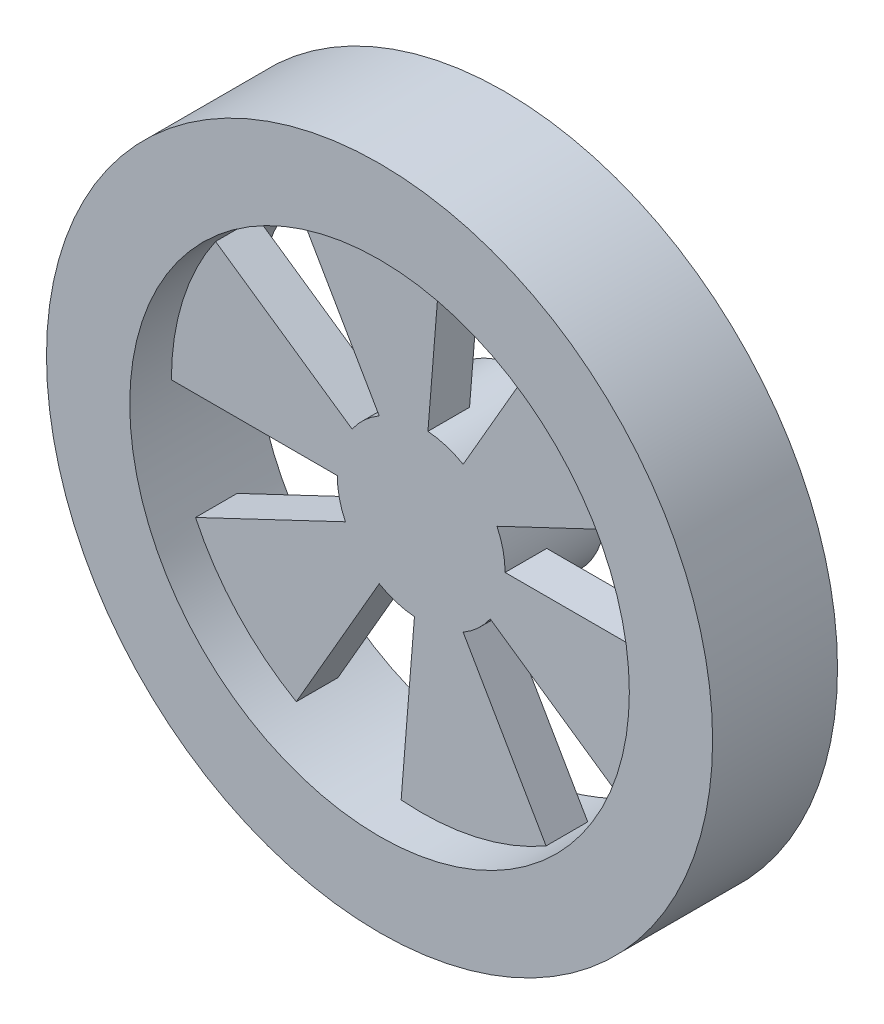
SolidWorks part; units mm, degrees
ref_plane "Front Plane" through (0, 0, 0) normal (0, 0, 1) x (1, 0, 0)
ref_plane "Top Plane" through (0, 0, 0) normal (0, 1, 0) x (1, 0, 0)
ref_plane "Right Plane" through (0, 0, 0) normal (1, 0, 0) x (0, 0, -1)
sketch "Sketch1" plane through (0, 0, 0) normal (0, 0, 1) x (1, 0, 0)
  circle A0 centre (0, 0) radius 40
  dimension "D1" = 80
extrude "Boss-Extrude1" add sketch "Sketch1" along normal blind 15
sketch "Sketch2" plane through (0, 0, 0) normal (0, 0, 1) x (1, 0, 0)
  circle A0 centre (0, 0) radius 1
  circle A1 centre (0, 0) radius 7.5
  dimension "D1" = 2
  dimension "D2" = 15
extrude "Boss-Extrude2" add sketch "Sketch2" against normal blind 20
sketch "Sketch4" plane through (0, 0, -20) normal (0, 0, -1) x (-1, 0, 0)
  circle A0 centre (0, 0) radius 3.175
  dimension "D1" = 6.35
extrude "Cut-Extrude1" cut sketch "Sketch4" against normal blind 1.6
sketch "Sketch5" plane through (0, 0, 0) normal (1, 0, 0) x (0, 0, -1)
  line L0 (0, 55) -> (0, -55) construction
  line L1 (0, 7.5) -> (2, 7.5)
  line L2 (0, 7.5) -> (0, 10.0764)
  line L3 (0, 10.0764) -> (2, 10.0764)
  line L4 (2, 7.5) -> (2, 10.0764)
  line L5 (20, 7.5) -> (0, 7.5) construction
  line L6 (2, 10.0764) -> (12, 10.0764) construction
  line L7 (12, 10.0764) -> (12, 4.3117) construction
  line L9 (12, 7.5) -> (13.5, 7.5)
  line L10 (12, 7.5) -> (12, 6.5)
  line L11 (12, 6.5) -> (13.5, 6.5)
  line L12 (13.5, 7.5) -> (13.5, 6.5)
  dimension "D1" = 10
  dimension "D2" = 2
  dimension "D3" = 1
  dimension "D4" = 1.5
ref_axis "Axis1" through (0, 0, -21.75) along (0, 0, 1)
revolve "Revolve2" add sketch "Sketch5" angle 360 about axis through (0, 0, -21.75) along (0, 0, 1)
revolve "Cut-Revolve1" cut sketch "Sketch5<4>" angle 360 about axis through (0, 0, -21.75) along (0, 0, 1)
sketch "Sketch5<4>" plane through (0, 0, 0) normal (1, 0, 0) x (0, 0, -1) same geometry as "Sketch5"
sketch "Sketch6" plane through (0, 0, 0) normal (0, 0, -1) x (-1, 0, 0)
  circle A0 centre (0, 0) radius 30
  circle A1 centre (0, 0) radius 10.0764
  dimension "D1" = 60
extrude "Cut-Extrude2" cut sketch "Sketch6" against normal blind 5
sketch "Sketch7" plane through (0, 0, 15) normal (0, 0, 1) x (1, 0, 0)
  circle A0 centre (0, 0) radius 30
  dimension "D1" = 60
extrude "Cut-Extrude3" cut sketch "Sketch7" against normal blind 5
sketch "Sketch8" plane through (0, 0, 5) normal (0, 0, -1) x (-1, 0, 0)
  line L0 (-10.0764, 0) -> (-30, 0)
  line L1 (19.25, 0) -> (-19.25, 0) construction
  line L2 (-27.1012, 12.8657) -> (-9.1028, 4.3213)
  line L3 (-2.4086, 29.9032) -> (-0.809, 10.0439)
  line L4 (-5.0382, 8.7264) -> (-15, 25.9808)
  line L5 (24.6926, 17.0375) -> (8.2938, 5.7226)
  line L6 (5.0382, 8.7264) -> (15, 25.9808)
  line L7 (27.1012, -12.8657) -> (9.1028, -4.3213)
  line L8 (10.0764, 0) -> (30, 0)
  line L9 (2.4086, -29.9032) -> (0.809, -10.0439)
  line L10 (5.0382, -8.7264) -> (15, -25.9808)
  line L11 (-24.6926, -17.0375) -> (-8.2938, -5.7226)
  line L12 (-5.0382, -8.7264) -> (-15, -25.9808)
  circle A0 centre (0, 0) radius 10.0764 construction
  circle A1 centre (0, 0) radius 30 construction
  circle A2 centre (0, 0) radius 10.0764 construction
  arc A3 (-27.1012, 12.8657) -> (-30, 0) centre (0, 0) ccw
  arc A4 (-9.1028, 4.3213) -> (-10.0764, 0) centre (0, 0) ccw
  arc A5 (-0.809, 10.0439) -> (-5.0382, 8.7264) centre (0, 0) ccw
  arc A6 (-2.4086, 29.9032) -> (-15, 25.9808) centre (0, 0) ccw
  arc A7 (8.2938, 5.7226) -> (5.0382, 8.7264) centre (0, 0) ccw
  arc A8 (24.6926, 17.0375) -> (15, 25.9808) centre (0, 0) ccw
  arc A9 (9.1028, -4.3213) -> (10.0764, 0) centre (0, 0) ccw
  arc A10 (27.1012, -12.8657) -> (30, 0) centre (0, 0) ccw
  arc A11 (0.809, -10.0439) -> (5.0382, -8.7264) centre (0, 0) ccw
  arc A12 (2.4086, -29.9032) -> (15, -25.9808) centre (0, 0) ccw
  arc A13 (-8.2938, -5.7226) -> (-5.0382, -8.7264) centre (0, 0) ccw
  arc A14 (-24.6926, -17.0375) -> (-15, -25.9808) centre (0, 0) ccw
  point P37 (0, 0)
  dimension "D1" = 6
extrude "Cut-Extrude4" cut sketch "Sketch8" against normal blind 5
